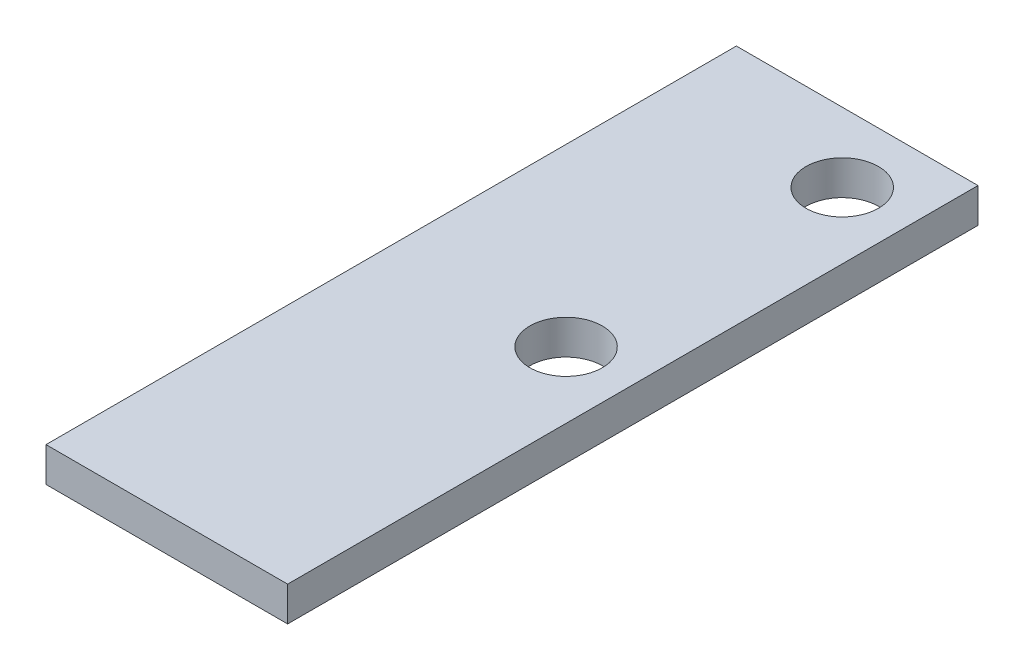
SolidWorks part; units mm, degrees
ref_plane "Front Plane" through (0, 0, 0) normal (0, 0, 1) x (1, 0, 0)
ref_plane "Top Plane" through (0, 0, 0) normal (0, 1, 0) x (1, 0, 0)
ref_plane "Right Plane" through (0, 0, 0) normal (1, 0, 0) x (0, 0, -1)
sketch "Sketch1" plane through (0, 0, 0) normal (1, 0, 0) x (0, 0, -1)
  line L0 (0, 0) -> (13, 0)
  line L1 (13, 0) -> (13, -7.5)
  line L2 (0, 0) -> (0, -7.5)
  line L3 (0, -7.5) -> (3.05, -7.5)
  line L4 (3.05, -7.5) -> (3.05, -17.6)
  line L5 (3.05, -17.6) -> (4.55, -17.6)
  line L6 (8.55, -17.6) -> (8.55, -18.35)
  line L7 (8.05, -18.35) -> (2.55, -18.35)
  line L8 (2.55, -17.8508) -> (2.55, -10.3717)
  line L9 (2.55, -8) -> (0, -8)
  line L10 (0, -8) -> (-1.5, -19.75)
  line L11 (13, -7.5) -> (8.05, -7.5)
  line L12 (8.05, -7.5) -> (8.05, -11.3)
  line L13 (8.05, -11.3) -> (14.05, -11.3)
  line L14 (14.05, -11.3) -> (14.05, -10.55)
  line L15 (13.4618, -10.55) -> (10.5033, -10.55)
  line L16 (8.55, -10.55) -> (8.55, -8)
  line L17 (8.55, -8) -> (9.9495, -8)
  line L18 (15.55, -9.65) -> (15.55, -15.95)
  line L19 (15.55, -15.95) -> (4.55, -15.95)
  line L20 (4.55, -15.95) -> (4.55, -16.7)
  line L21 (5.1412, -16.7) -> (8.05, -16.7)
  line L22 (10.05, -16.7) -> (10.05, -19.25)
  line L23 (10.05, -19.25) -> (8.55, -19.25)
  line L24 (1.65, -19.25) -> (1.65, -18.35)
  line L25 (1.8597, -9.5) -> (0.9, -9.5)
  line L26 (0.9, -9.5) -> (0.9, -19.75)
  line L27 (0.9, -19.75) -> (19.35, -19.75)
  line L28 (15.55, -9.65) -> (14.05, -9.65)
  line L29 (10.05, -9.65) -> (10.05, -8.9)
  line L30 (10.5033, -8.9) -> (15.55, -8.9)
  line L31 (16.05, -9.5) -> (16.05, -17.2155)
  line L32 (16.95, -8) -> (16.95, -8.9)
  line L33 (16.95, -17.75) -> (17.7, -17.75)
  line L34 (17.7, -17.2155) -> (17.7, -9.748)
  line L35 (17.7, -8) -> (20.25, -8)
  line L36 (16.05, -19.25) -> (18.6, -19.25)
  line L37 (18.6, -19.25) -> (18.6, -17.75)
  line L38 (18.6, -9.5) -> (19.35, -9.5)
  line L39 (19.35, -9.5) -> (19.35, -19.75)
  line L45 (0, -21.25) -> (21.75, -21.25)
  line L47 (21.75, -21.25) -> (21.75, -19.75)
  line L49 (20.25, -8) -> (21.75, -19.75)
  line L51 (-1.5, -19.75) -> (-1.5, -26.08)
  line L52 (-1.5, -26.08) -> (3, -26.08)
  line L53 (3, -26.08) -> (3, -24.58)
  line L54 (3, -24.58) -> (0, -24.58)
  line L55 (0, -24.58) -> (0, -21.25)
  line L56 (1.65, -17.8508) -> (1.65, -10.3717)
  line L57 (1.8597, -9.5) -> (1.8597, -10.3717)
  line L58 (1.8597, -10.3717) -> (1.65, -10.3717)
  line L59 (2.55, -9.5) -> (2.2967, -9.5)
  line L60 (2.2967, -9.5) -> (2.2967, -10.3717)
  line L61 (2.2967, -10.3717) -> (2.55, -10.3717)
  line L62 (2.55, -18.35) -> (2.2967, -18.35)
  line L63 (2.2967, -18.35) -> (2.2967, -17.8508)
  line L64 (2.2967, -17.8508) -> (2.55, -17.8508)
  line L65 (1.65, -17.8508) -> (1.8597, -17.8508)
  line L66 (1.8597, -17.8508) -> (1.8597, -18.35)
  line L67 (1.8597, -18.35) -> (1.65, -18.35)
  line L68 (2.55, -18.35) -> (2.55, -18.653)
  line L69 (2.55, -18.653) -> (3.05, -18.653)
  line L70 (3.05, -18.653) -> (3.05, -18.35)
  line L71 (2.55, -19.25) -> (2.55, -19.0635)
  line L72 (2.55, -19.0635) -> (3.05, -19.0635)
  line L73 (3.05, -19.0635) -> (3.05, -19.25)
  line L74 (8.55, -19.25) -> (8.55, -19.0635)
  line L75 (8.55, -19.0635) -> (8.05, -19.0635)
  line L76 (8.05, -19.0635) -> (8.05, -19.25)
  line L77 (8.55, -18.35) -> (8.55, -18.653)
  line L78 (8.55, -18.653) -> (8.05, -18.653)
  line L79 (8.05, -18.653) -> (8.05, -18.35)
  line L80 (8.55, -17.6) -> (8.55, -17.3457)
  line L81 (8.55, -17.3457) -> (8.05, -17.3457)
  line L82 (8.05, -17.3457) -> (8.05, -17.6)
  line L83 (8.55, -16.7) -> (8.55, -16.9243)
  line L84 (8.55, -16.9243) -> (8.05, -16.9243)
  line L85 (8.05, -16.9243) -> (8.05, -16.7)
  line L86 (4.55, -16.7) -> (4.55, -16.9243)
  line L87 (4.55, -16.9243) -> (5.1412, -16.9243)
  line L88 (5.1412, -16.9243) -> (5.1412, -16.7)
  line L89 (4.55, -17.6) -> (4.55, -17.3457)
  line L90 (4.55, -17.3457) -> (5.1412, -17.3457)
  line L91 (5.1412, -17.3457) -> (5.1412, -17.6)
  line L92 (14.05, -10.55) -> (14.05, -10.2484)
  line L93 (14.05, -10.2484) -> (13.4618, -10.2484)
  line L94 (13.4618, -10.2484) -> (13.4618, -10.55)
  line L95 (14.05, -9.65) -> (14.05, -9.932)
  line L96 (14.05, -9.932) -> (13.4618, -9.932)
  line L97 (13.4618, -9.932) -> (13.4618, -9.65)
  line L98 (10.05, -10.55) -> (10.05, -10.2484)
  line L99 (10.05, -10.2484) -> (10.5033, -10.2484)
  line L100 (10.5033, -10.2484) -> (10.5033, -10.55)
  line L101 (10.05, -9.65) -> (10.05, -9.932)
  line L102 (10.05, -9.932) -> (10.5033, -9.932)
  line L103 (10.5033, -9.932) -> (10.5033, -9.65)
  line L104 (10.05, -8.9) -> (10.05, -8.6188)
  line L105 (10.05, -8.6188) -> (10.5033, -8.6188)
  line L106 (10.5033, -8.6188) -> (10.5033, -8.9)
  line L107 (9.9495, -8) -> (9.9495, -8.3024)
  line L108 (9.9495, -8.3024) -> (10.5033, -8.3024)
  line L109 (10.5033, -8.3024) -> (10.5033, -8)
  line L110 (16.05, -8.9) -> (16.05, -8.6188)
  line L111 (16.05, -8.6188) -> (15.55, -8.6188)
  line L112 (15.55, -8.6188) -> (15.55, -8.9)
  line L113 (16.05, -8) -> (16.05, -8.3024)
  line L114 (16.05, -8.3024) -> (15.55, -8.3024)
  line L115 (15.55, -8.3024) -> (15.55, -8)
  line L116 (16.05, -8.9) -> (16.2938, -8.9)
  line L117 (16.2938, -8.9) -> (16.2938, -9.5)
  line L118 (16.2938, -9.5) -> (16.05, -9.5)
  line L119 (16.95, -8.9) -> (16.6894, -8.9)
  line L120 (16.6894, -8.9) -> (16.6894, -9.5)
  line L121 (16.6894, -9.5) -> (16.95, -9.5)
  line L122 (16.95, -17.75) -> (16.6894, -17.75)
  line L123 (16.6894, -17.75) -> (16.6894, -17.2155)
  line L124 (16.6894, -17.2155) -> (16.95, -17.2155)
  line L125 (16.05, -17.75) -> (16.2938, -17.75)
  line L126 (16.2938, -17.75) -> (16.2938, -17.2155)
  line L127 (16.2938, -17.2155) -> (16.05, -17.2155)
  line L128 (17.7, -17.75) -> (17.9503, -17.75)
  line L129 (17.9503, -17.75) -> (17.9503, -17.2155)
  line L130 (17.9503, -17.2155) -> (17.7, -17.2155)
  line L131 (18.6, -17.75) -> (18.2565, -17.75)
  line L132 (18.2565, -17.75) -> (18.2565, -17.2155)
  line L133 (18.2565, -17.2155) -> (18.6, -17.2155)
  line L134 (18.6, -9.5) -> (18.2565, -9.5)
  line L135 (18.2565, -9.5) -> (18.2565, -9.748)
  line L136 (18.2565, -9.748) -> (18.6, -9.748)
  line L137 (17.7, -9.5) -> (17.9503, -9.5)
  line L138 (17.9503, -9.5) -> (17.9503, -9.748)
  line L139 (17.9503, -9.748) -> (17.7, -9.748)
  line L140 (2.55, -9.5) -> (2.55, -8)
  line L141 (5.1412, -17.6) -> (8.05, -17.6)
  line L142 (8.55, -16.7) -> (10.05, -16.7)
  line L143 (2.55, -19.25) -> (1.65, -19.25)
  line L144 (8.05, -19.25) -> (3.05, -19.25)
  line L145 (10.5033, -8) -> (15.55, -8)
  line L146 (10.05, -10.55) -> (8.55, -10.55)
  line L147 (13.4618, -9.65) -> (10.5033, -9.65)
  line L148 (16.05, -8) -> (16.95, -8)
  line L149 (16.95, -9.5) -> (16.95, -17.2155)
  line L150 (17.7, -9.5) -> (17.7, -8)
  line L151 (18.6, -17.2155) -> (18.6, -9.748)
  line L152 (16.05, -17.75) -> (16.05, -19.25)
  dimension "D2" = 2.55
  dimension "D3" = 0.9
  dimension "D5" = 6
  dimension "D6" = 1.5
  dimension "D7" = 6
  dimension "D8" = 2.55
  dimension "D9" = 0.9
  dimension "D10" = 0.75
  dimension "D11" = 2.55
  dimension "D12" = 7.5
  dimension "D13" = 0.5
  dimension "D14" = 1.5
  dimension "D15" = 11.25
  dimension "D16" = 0.5
  dimension "D17" = 1.5
  dimension "D20" = 13
  dimension "D21" = 0.5
  dimension "D22" = 2.55
  dimension "D24" = 0.75
  dimension "D25" = 0.75
  dimension "D26" = 1.5
  dimension "D27" = 0.5
  dimension "D29" = 0.9
  dimension "D28" = 1.5
  dimension "D30" = 1.5
  dimension "D31" = 0.75
  dimension "D18" = 1.5
  dimension "D19" = 4.5
  dimension "D32" = 1.5
  dimension "D33" = 3.33
extrude "Boss-Extrude1" add sketch "Sketch1" along normal blind 5.18 rebuild error yes
sketch "Sketch2" plane through (0, 0, 0) normal (0, 0, 1) x (1, 0, 0)
  line L0 (5.18, 0) -> (5.18, -7.5) construction
  line L1 (5.18, -0.85) -> (1.73, -0.85)
  line L2 (5.18, -0.85) -> (5.18, -6)
  line L3 (5.18, -6) -> (1.73, -6)
  line L4 (1.73, -0.85) -> (1.73, -6)
  line L6 (5.18, -7.5) -> (0, -7.5) construction
  line L7 (5.18, 0) -> (0, 0) construction
  dimension "D1" = 3.45
  dimension "D2" = 1.5
  dimension "D3" = 0.85
extrude "Cut-Extrude1" cut sketch "Sketch2" against normal up to next rebuild error yes
sketch "Sketch3" plane through (0, -21.25, 0) normal (0, -1, 0) x (1, 0, 0)
  line L0 (0, 1.5) -> (0, -3) construction
  line L1 (0, -30) -> (10.5, -30)
  line L2 (0, -30) -> (0, 0)
  line L3 (0, 0) -> (10.5, 0)
  line L4 (10.5, -30) -> (10.5, 0)
  line L6 (5.18, 0) -> (5.18, -21.75) construction
  line L7 (5.18, 1.5) -> (0, 1.5) construction
  circle A0 centre (7.62, -14.98) radius 1.575
  circle A1 centre (7.62, -26.98) radius 1.575
  dimension "D3" = 3.15
  dimension "D1" = 10.5
  dimension "D2" = 16.48
  dimension "D4" = 12
  dimension "D5" = 30
  dimension "D6" = 2.44
extrude "Boss-Extrude2" add sketch "Sketch3" against normal blind 1.5
sketch "Sketch7" plane through (0, 0, 0) normal (-1, 0, 0) x (0, 0, 1)
  line L0 (-13, 0) -> (0, 0) construction
  line L1 (0, 0) -> (0, -7.5) construction
  circle A0 centre (-3.25, -3.5) radius 1.575
  circle A1 centre (-9.75, -3.5) radius 1.575
  dimension "D1" = 3.15
  dimension "D2" = 3.5
  dimension "D3" = 3.25
  dimension "D4" = 6.5
extrude "Cut-Extrude3" cut sketch "Sketch7" against normal up to next rebuild error yes
mirror "Mirror3" [suppressed] of bodies 103 105
delete or keep bodies "Body-Delete/Keep 1" [suppressed] type delete bodies bodies 103
equation "\"FlexureWidth\"= 0.90"
equation "\"FlexureGap\"= 0.75"
equation "\"DoubleFlexureWidth\"= 2 * \"FlexureWidth\" + \"FlexureGap\""
equation "\"D2@Sketch1\"=\"DoubleFlexureWidth\""
equation "\"D3@Sketch1\"=\"FlexureWidth\""
equation "\"HorizontalFlexureLength\"= 6"
equation "\"FlexureJointWidth\"= 1.5"
equation "\"D5@Sketch1\"=\"HorizontalFlexureLength\""
equation "\"D6@Sketch1\"=\"FlexureJointWidth\""
equation "\"D7@Sketch1\"=\"HorizontalFlexureLength\""
equation "\"D8@Sketch1\"=\"DoubleFlexureWidth\""
equation "\"D9@Sketch1\"=\"FlexureWidth\""
equation "\"D10@Sketch1\"=\"FlexureGap\""
equation "\"D11@Sketch1\"=\"DoubleFlexureWidth\""
equation "\"HeadHeight\"= 7.5"
equation "\"VerticalFlexureLength\"= 11.25"
equation "\"MinGap\"= 0.5"
equation "\"D12@Sketch1\"=\"HeadHeight\""
equation "\"D13@Sketch1\"=\"MinGap\""
equation "\"D14@Sketch1\"=\"FlexureJointWidth\""
equation "\"D15@Sketch1\"=\"VerticalFlexureLength\""
equation "\"D16@Sketch1\"=\"MinGap\""
equation "\"D17@Sketch1\"=\"FlexureJointWidth\""
equation "\"BaseplateHeight+Tolerance\"= 3.33"
equation "\"HeadWidth\"= 13"
equation "\"D20@Sketch1\"=\"HeadWidth\""
equation "\"D21@Sketch1\"=\"MinGap\""
equation "\"D22@Sketch1\"=\"DoubleFlexureWidth\""
equation "\"D24@Sketch1\"=\"FlexureGap\""
equation "\"D25@Sketch1\"=\"FlexureGap\""
equation "\"D26@Sketch1\"=\"FlexureJointWidth\""
equation "\"D27@Sketch1\"=\"MinGap\""
equation "\"D29@Sketch1\"=\"FlexureWidth\""
equation "\"D28@Sketch1\"=\"FlexureJointWidth\""
equation "\"D30@Sketch1\"=\"FlexureJointWidth\""
equation "\"D31@Sketch1\"=\"FlexureGap\""
equation "\"D1@Boss-Extrude1\"=5.18"
equation "\"D32@Sketch1\"=\"FlexureJointWidth\""
equation "\"D18@Sketch1\"=\"FlexureJointWidth\""
equation "\"FlexureCollarWidth\"= 1.1"
